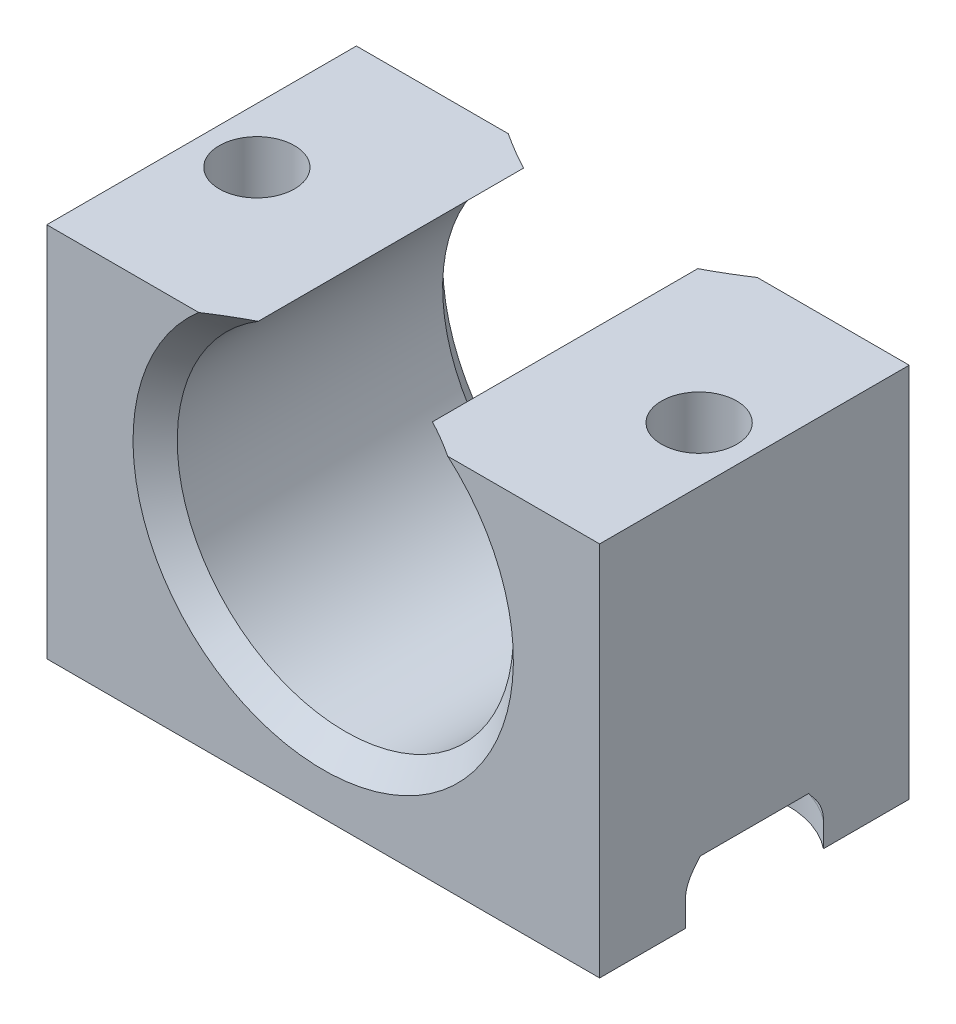
SolidWorks part; units mm, degrees
material "6061 Alloy"
ref_plane "Front Plane" through (0, 0, 0) normal (0, 0, 1) x (1, 0, 0)
ref_plane "Top Plane" through (0, 0, 0) normal (0, 1, 0) x (1, 0, 0)
ref_plane "Right Plane" through (0, 0, 0) normal (1, 0, 0) x (0, 0, -1)
sketch "Sketch1" plane through (0, 0, 0) normal (0, 1, 0) x (1, 0, 0)
  line L0 (0, 0) -> (0, 14)
  line L1 (0, 0) -> (25, 0)
  line L2 (0, 14) -> (25, 14)
  line L3 (25, 0) -> (25, 14)
  dimension "D1" = 14
  dimension "D2" = 25
extrude "Boss-Extrude1" add sketch "Sketch1" along normal blind 17
sketch "Sketch2" plane through (0, 0, 0) normal (0, 0, 1) x (1, 0, 0)
  line L0 (0, 17) -> (25, 17) construction
  line L1 (0, 0) -> (25, 0) construction
  line L2 (0, 17) -> (0, 0) construction
  arc A0 (8.5617, 17) -> (16.4383, 17) centre (12.5, 10.5) ccw
  dimension "D1" = 7.6
  dimension "D2" = 10.5
  dimension "D3" = 12.5
extrude "Cut-Extrude1" cut sketch "Sketch2" against normal through all and the other way through all
hole_wizard "Ø3.4 (3.4) Diameter Hole1" positions "Sketch4" profile "Sketch3" hole size "Ø3.4" standard "ANSI Metric" end condition through all
sketch "Sketch4" plane through (0, 17, 0) normal (0, 1, 0) x (1, 0, 0)
  line L0 (8.5617, 14) -> (0, 14) construction
  line L1 (0, 14) -> (0, 0) construction
  line L2 (25, 0) -> (25, 14) construction
  point P0 (22.5, 7)
  point P2 (2.5, 7)
  dimension "D1" = 7
  dimension "D2" = 2.5
  dimension "D3" = 2.5
sketch "Sketch3" plane through (22.5, 17, -7) normal (1, 0, 0) x (0, 0, 1)
  line L0 (0, 0) -> (0, 17)
  line L1 (0, 17) -> (1.7, 17)
  line L2 (1.7, 17) -> (1.7, 0)
  line L5 (1.7, 0) -> (0, 0)
  line L11 (0, -6.35) -> (0, 107.95) construction
  dimension "Thru Hole Dia." = 3.4
  dimension "Thru Hole Depth" = 17
sketch "Sketch5" plane through (0, 0, 0) normal (0, -1, 0) x (1, 0, 0)
  circle A0 centre (2.5, -7) radius 4
  circle A1 centre (22.5, -7) radius 4
  dimension "D1" = 8
extrude "Cut-Extrude2" cut sketch "Sketch5" against normal blind 2.5
chamfer "Chamfer1" distance 1 angle 45 2 edges at (12.5, 2.9, -14) (12.5, 2.9, 0)
chamfer "Chamfer2" distance 0.5 angle 60 2 edges at (6.5, 2.5, -7) (18.5, 2.5, -7) first distance on face at (2.5, 2.5, -8.7) first distance on face at (22.5, 2.5, -8.7)
fillet "Fillet1" radius 2 2 edges at (6.5, 1.634, -7) (18.5, 1.634, -7)
